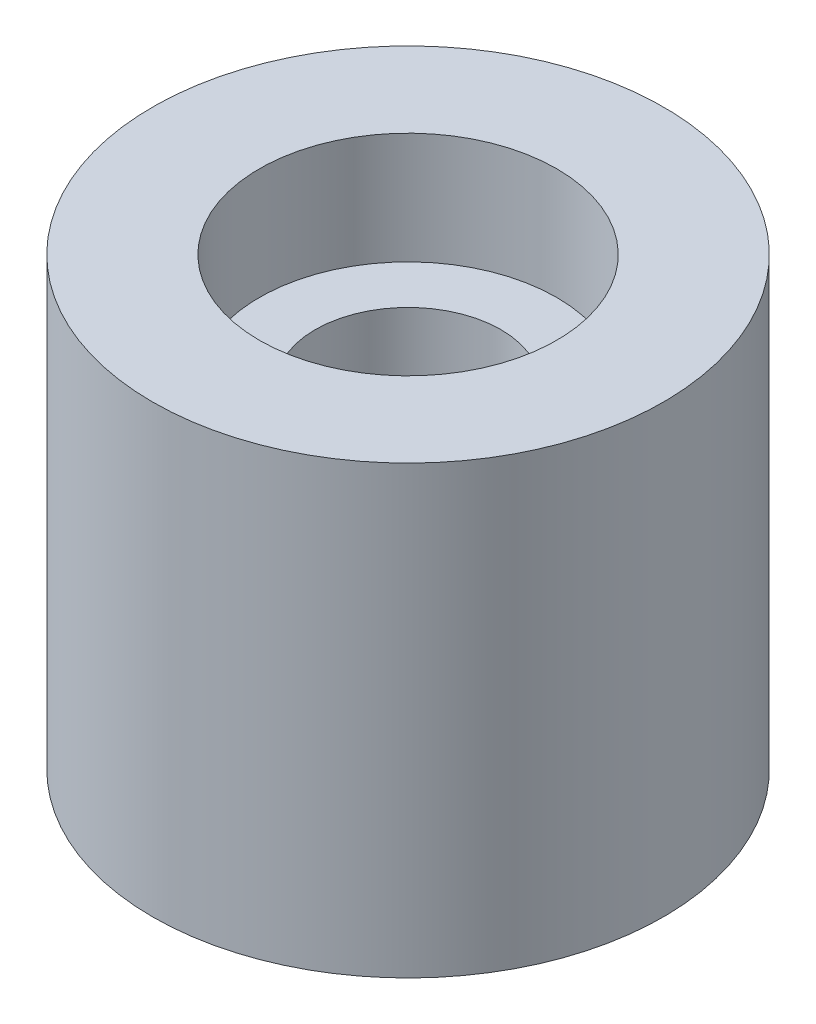
SolidWorks part; units mm, degrees
ref_plane "前视基准面" through (0, 0, 0) normal (0, 0, 1) x (1, 0, 0)
ref_plane "上视基准面" through (0, 0, 0) normal (0, 1, 0) x (1, 0, 0)
ref_plane "右视基准面" through (0, 0, 0) normal (1, 0, 0) x (0, 0, -1)
other "Configuration Table"
sketch "草图1" plane through (0, 0, 0) normal (0, 1, 0) x (1, 0, 0)
  circle A0 centre (0, 0) radius 2.75
  dimension "D2" = 5.5
extrude "凸台-拉伸1" add sketch "草图1" along normal blind 4.8 contours A0
sketch "草图2" plane through (0, 4.8, 0) normal (0, 1, 0) x (1, 0, 0)
  circle A0 centre (0, 0) radius 1.6
  circle A1 centre (0, 0) radius 1
  dimension "D1" = 3.2
  dimension "D2" = 2
extrude "切除-拉伸1" cut sketch "草图2" against normal through all contours A1
extrude "切除-拉伸2" cut sketch "草图2<3>" against normal blind 1.2 contours A0
sketch "草图2<3>" plane through (0, 4.8, 0) normal (0, 1, 0) x (1, 0, 0) same geometry as "草图2"
extrude "切除-拉伸3" cut sketch "草图2<4>" along normal blind 1.2 from surface contours A0 starting at face at (0, 0, 1)
sketch "草图2<4>" plane through (0, 4.8, 0) normal (0, 1, 0) x (1, 0, 0) same geometry as "草图2"
